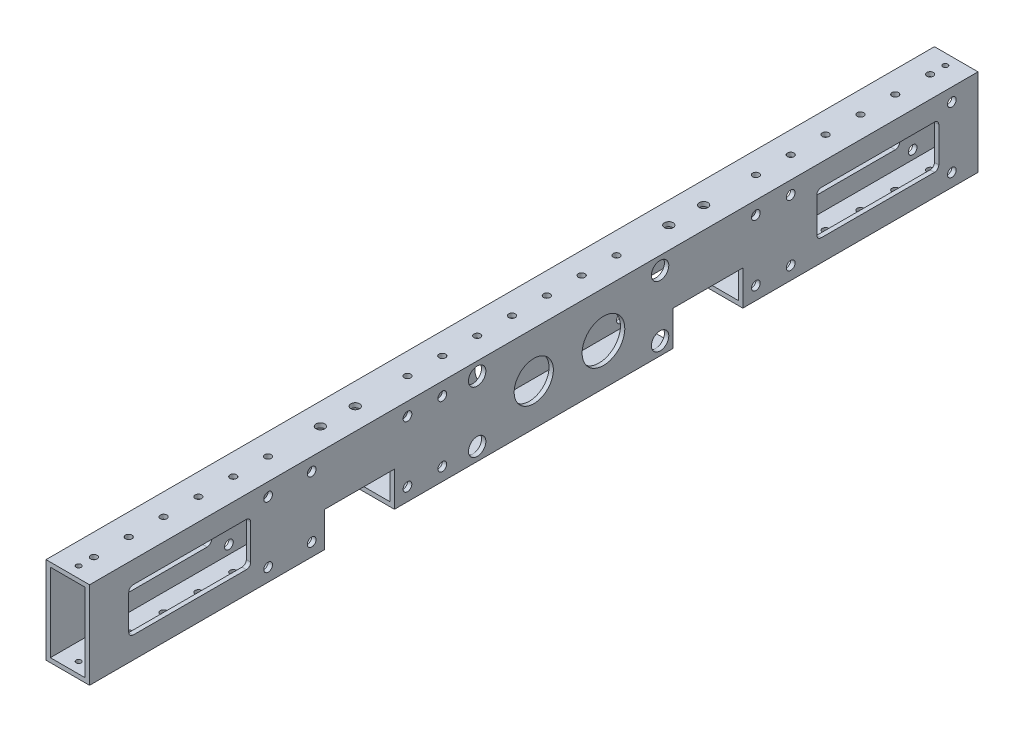
SolidWorks part; units mm, degrees
ref_plane "Front Plane" through (0, 0, 0) normal (0, 0, 1) x (1, 0, 0)
ref_plane "Top Plane" through (0, 0, 0) normal (0, 1, 0) x (1, 0, 0)
ref_plane "Right Plane" through (0, 0, 0) normal (1, 0, 0) x (0, 0, -1)
sketch "Sketch1" plane through (0, 0, 0) normal (0, 0, 1) x (1, 0, 0)
  line L1 (-12.1647, 2.5103) -> (19.5853, 2.5103)
  line L2 (-12.1647, 2.5103) -> (-12.1647, -60.9897)
  line L3 (-12.1647, -60.9897) -> (19.5853, -60.9897)
  line L4 (19.5853, 2.5103) -> (19.5853, -60.9897)
  line L5 (-8.9897, -0.6647) -> (16.4103, -0.6647)
  line L6 (-8.9897, -0.6647) -> (-8.9897, -57.8147)
  line L7 (-8.9897, -57.8147) -> (16.4103, -57.8147)
  line L8 (16.4103, -0.6647) -> (16.4103, -57.8147)
  dimension "D1" = 63.5
  dimension "D2" = 31.75
  dimension "D3" = 3.175
  dimension "D4" = 3.175
  dimension "D5" = 3.175
  dimension "D6" = 3.175
extrude "Boss-Extrude1" add sketch "Sketch1" along normal blind 647.7
sketch "Sketch3" plane through (-12.1647, 0, 0) normal (-1, 0, 0) x (0, 0, 1)
  line L0 (0, 2.5103) -> (0, -60.9897) construction
  line L1 (31.75, -13.3647) -> (114.3, -13.3647)
  line L2 (28.575, -16.5397) -> (28.575, -41.9397)
  line L3 (31.75, -45.1147) -> (114.3, -45.1147)
  line L4 (117.475, -16.5397) -> (117.475, -41.9397)
  line L5 (647.7, 2.5103) -> (0, 2.5103) construction
  line L6 (647.7, -60.9897) -> (0, -60.9897) construction
  line L7 (323.85, 2.5103) -> (323.85, -60.9897) construction
  line L8 (530.225, -16.5397) -> (530.225, -41.9397)
  line L9 (615.95, -45.1147) -> (533.4, -45.1147)
  line L10 (619.125, -16.5397) -> (619.125, -41.9397)
  line L11 (615.95, -13.3647) -> (533.4, -13.3647)
  line L12 (647.7, 2.5103) -> (647.7, -60.9897) construction
  line L13 (171.45, -60.9897) -> (222.25, -60.9897)
  line L14 (171.45, -60.9897) -> (171.45, -35.5897)
  line L15 (171.45, -35.5897) -> (222.25, -35.5897)
  line L16 (222.25, -60.9897) -> (222.25, -35.5897)
  line L17 (425.45, -60.9897) -> (476.25, -60.9897)
  line L18 (476.25, -60.9897) -> (476.25, -35.5897)
  line L19 (476.25, -35.5897) -> (425.45, -35.5897)
  line L20 (425.45, -60.9897) -> (425.45, -35.5897)
  line L22 (0, -29.2397) -> (647.7, -29.2397) construction
  line L23 (0, -60.9897) -> (0, 2.5103) construction
  line L26 (647.7, -60.9897) -> (647.7, 2.5103) construction
  arc A0 (28.575, -41.9397) -> (31.75, -45.1147) centre (31.75, -41.9397) ccw
  arc A1 (114.3, -45.1147) -> (117.475, -41.9397) centre (114.3, -41.9397) ccw
  arc A2 (114.3, -13.3647) -> (117.475, -16.5397) centre (114.3, -16.5397) cw
  arc A3 (31.75, -13.3647) -> (28.575, -16.5397) centre (31.75, -16.5397) ccw
  arc A4 (615.95, -13.3647) -> (619.125, -16.5397) centre (615.95, -16.5397) cw
  arc A5 (533.4, -13.3647) -> (530.225, -16.5397) centre (533.4, -16.5397) ccw
  arc A6 (533.4, -45.1147) -> (530.225, -41.9397) centre (533.4, -41.9397) cw
  arc A7 (619.125, -41.9397) -> (615.95, -45.1147) centre (615.95, -41.9397) cw
  line M7 (0, -60.9897) -> (647.7, -60.9897)
  dimension "D5" = 3.175
  dimension "D1" = 28.575
  dimension "D4" = 88.9
  dimension "D6" = 25.4
  dimension "D7" = 50.8
  dimension "D8" = 171.45
  dimension "D9" = 50.8
  dimension "D10" = 25.4
  dimension "D11" = 171.45
  dimension "D2" = 31.75
  dimension "D3" = 15.875
extrude "Cut-Extrude1" cut sketch "Sketch3" against normal up to surface (31.75 mm away) contours L1 A3 L2 A0 L3 A1 L4 A2 | A7 L10 A4 L11 A5 L8 A6 L9 | L16 L15 L14 M7 | L20 L18 L19 M7 region at (-12.1647, -29.2397, 73.025) region at (-12.1647, -29.2397, 574.675) region at (-12.1647, -48.2897, 196.85) region at (-12.1647, -48.2897, 450.85) up to face at (19.5853, -29.2397, 323.85)
sketch "Sketch6" plane through (19.5853, 0, 0) normal (1, 0, 0) x (0, 0, -1)
  line L0 (-647.7, -30.8272) -> (0, -30.8272) construction
  line L1 (-425.45, -60.9897) -> (-222.25, -60.9897) construction
  line L2 (-365.125, -7.0147) -> (-231.775, -7.0147) construction
  line L3 (-365.125, -7.0147) -> (-365.125, -51.4647) construction
  line L4 (-647.7, -60.9897) -> (-647.7, 2.5103) construction
  line L5 (-365.125, -51.4647) -> (-231.775, -51.4647) construction
  line L6 (-231.775, -7.0147) -> (-231.775, -51.4647) construction
  line L7 (0, -60.9897) -> (0, 2.5103) construction
  circle A0 centre (-323.85, -30.8272) radius 14.2875
  circle A1 centre (-273.05, -30.8272) radius 15.5575
  circle A2 centre (-365.125, -7.0147) radius 3.175
  circle A3 centre (-231.775, -7.0147) radius 3.175
  circle A4 centre (-365.125, -51.4647) radius 3.175
  circle A5 centre (-231.775, -51.4647) radius 3.175
  dimension "D1" = 28.575
  dimension "D4" = 50.8
  dimension "D6" = 20.6375
  dimension "D8" = 41.275
  dimension "D7" = 6.35
  dimension "D10" = 31.115
  dimension "D2" = 30.1625
  dimension "D3" = 323.85
  dimension "D5" = 23.8125
  dimension "D9" = 92.075
extrude "Cut-Extrude2" cut sketch "Sketch6" against normal up to surface (31.75 mm away) up to face at (-12.1647, -41.9397, 323.85)
sketch "Sketch7" plane through (19.5853, 0, 0) normal (1, 0, 0) x (0, 0, -1)
  circle A0 centre (-365.125, -7.0147) radius 6.35
  circle A1 centre (-365.125, -51.4647) radius 6.35
  circle A2 centre (-231.775, -51.4647) radius 6.35
  circle A3 centre (-231.775, -7.0147) radius 6.35
  dimension "D1" = 12.7
extrude "Cut-Extrude3" cut sketch "Sketch7" against normal up to surface (28.575 mm away) up to face at (-8.9897, -16.5397, 323.85)
sketch "Sketch8" plane through (0, 2.5103, 0) normal (0, 1, 0) x (1, 0, 0)
  line L0 (-12.1647, -323.85) -> (19.5853, -323.85) construction
  line L1 (-12.1647, -171.45) -> (19.5853, -171.45) construction
  line L2 (-12.1647, -171.45) -> (-12.1647, -222.25) construction
  line L3 (-12.1647, -222.25) -> (19.5853, -222.25) construction
  line L4 (19.5853, -171.45) -> (19.5853, -222.25) construction
  line L5 (3.7103, -476.25) -> (3.7103, -425.45) construction
  line L6 (-12.1647, -647.7) -> (-12.1647, 0) construction
  line L7 (19.5853, -647.7) -> (19.5853, 0) construction
  line L8 (19.5853, 0) -> (-12.1647, 0) construction
  line L9 (3.7103, -171.45) -> (3.7103, -222.25) construction
  line L10 (19.5853, -476.25) -> (19.5853, -425.45) construction
  line L11 (-12.1647, -425.45) -> (19.5853, -425.45) construction
  line L12 (-12.1647, -476.25) -> (-12.1647, -425.45) construction
  line L13 (-12.1647, -476.25) -> (19.5853, -476.25) construction
  circle A0 centre (3.7103, -184.15) radius 3.175
  circle A1 centre (3.7103, -209.55) radius 3.175
  circle A2 centre (3.7103, -438.15) radius 3.175
  circle A3 centre (3.7103, -463.55) radius 3.175
  dimension "D4" = 6.35
  dimension "D1" = 50.8
  dimension "D2" = 31.75
  dimension "D3" = 171.45
  dimension "D5" = 25.4
  dimension "D6" = 12.7
extrude "Cut-Extrude4" cut sketch "Sketch8" against normal through all
sketch "Sketch9" plane through (0, 2.5103, 0) normal (0, 1, 0) x (1, 0, 0)
  line L0 (19.5853, 0) -> (-12.1647, 0) construction
  line L1 (19.5853, -647.7) -> (-12.1647, -647.7) construction
  line L2 (-12.1647, -647.7) -> (-12.1647, 0) construction
  circle A0 centre (3.7103, -639.7625) radius 1.8415
  circle A1 centre (3.7103, -7.9375) radius 1.8415
  dimension "D1" = 7.9375
  dimension "D3" = 3.683
  dimension "D4" = 3.683
  dimension "D2" = 7.9375
  dimension "D5" = 15.875
  dimension "D6" = 15.875
extrude "Cut-Extrude5" cut sketch "Sketch9" against normal up to surface (63.5 mm away) up to face at (3.7103, -60.9897, 561.975)
sketch "Sketch10" plane through (19.5853, 0, 0) normal (1, 0, 0) x (0, 0, -1)
  line L0 (-647.7, 2.5103) -> (0, 2.5103) construction
  line L1 (-527.05, 2.5103) -> (-476.25, 2.5103) construction
  line L2 (-527.05, 2.5103) -> (-527.05, -60.9897) construction
  line L3 (-527.05, -60.9897) -> (-476.25, -60.9897) construction
  line L4 (-476.25, 2.5103) -> (-476.25, -60.9897) construction
  line L5 (-647.7, -60.9897) -> (-476.25, -60.9897) construction
  line L7 (-476.25, -35.5897) -> (-476.25, -60.9897) construction
  line L8 (-415.925, -51.4647) -> (-390.525, -51.4647) construction
  line L9 (-517.525, -7.0147) -> (-485.775, -7.0147) construction
  line L10 (-517.525, -7.0147) -> (-517.525, -51.4647) construction
  line L11 (-517.525, -51.4647) -> (-485.775, -51.4647) construction
  line L12 (-485.775, -7.0147) -> (-485.775, -51.4647) construction
  line L13 (-425.45, -60.9897) -> (-381, -60.9897) construction
  line L14 (-425.45, -60.9897) -> (-425.45, 2.5103) construction
  line L15 (-425.45, 2.5103) -> (-381, 2.5103) construction
  line L16 (-381, -60.9897) -> (-381, 2.5103) construction
  line L17 (-390.525, -51.4647) -> (-390.525, -7.0147) construction
  line L18 (-415.925, -7.0147) -> (-390.525, -7.0147) construction
  line L19 (-415.925, -51.4647) -> (-415.925, -7.0147) construction
  line L20 (-161.925, -51.4647) -> (-136.525, -51.4647) construction
  line L21 (-171.45, -60.9897) -> (-127, -60.9897) construction
  line L22 (-171.45, -60.9897) -> (-171.45, 2.5103) construction
  line L23 (-171.45, 2.5103) -> (-127, 2.5103) construction
  line L24 (-127, -60.9897) -> (-127, 2.5103) construction
  line L25 (-136.525, -51.4647) -> (-136.525, -7.0147) construction
  line L26 (-161.925, -7.0147) -> (-136.525, -7.0147) construction
  line L27 (-161.925, -51.4647) -> (-161.925, -7.0147) construction
  line L28 (-171.45, -60.9897) -> (0, -60.9897) construction
  line L29 (-171.45, -35.5897) -> (-171.45, -60.9897) construction
  line L30 (0, -60.9897) -> (0, 2.5103) construction
  circle A0 centre (-517.525, -7.0147) radius 3.175
  circle A1 centre (-485.775, -7.0147) radius 3.175
  circle A2 centre (-485.775, -51.4647) radius 3.175
  circle A3 centre (-517.525, -51.4647) radius 3.175
  circle A4 centre (-415.925, -7.0147) radius 3.175
  circle A5 centre (-390.525, -7.0147) radius 3.175
  circle A6 centre (-415.925, -51.4647) radius 3.175
  circle A7 centre (-390.525, -51.4647) radius 3.175
  circle A8 centre (-161.925, -7.0147) radius 3.175
  circle A9 centre (-136.525, -7.0147) radius 3.175
  circle A10 centre (-161.925, -51.4647) radius 3.175
  circle A11 centre (-136.525, -51.4647) radius 3.175
  circle A12 centre (-19.05, -7.0147) radius 3.175
  circle A13 centre (-19.05, -51.4647) radius 3.175
  point P52 (0, 0)
  point P55 (0, 0)
  dimension "D2" = 6.35
  dimension "D1" = 50.8
  dimension "D3" = 9.525
  dimension "D5" = 9.525
  dimension "D4" = 9.525
  dimension "D6" = 9.525
  dimension "D7" = 44.45
  dimension "D9" = 44.45
  dimension "D10" = 9.525
  dimension "D11" = 19.05
  dimension "D8" = 9.525
extrude "Cut-Extrude6" cut sketch "Sketch10" against normal through all
sketch "Sketch11" plane through (0, -60.9897, 0) normal (0, -1, 0) x (1, 0, 0)
  line L0 (19.5853, 647.7) -> (19.5853, 476.25) construction
  line L1 (-12.1647, 647.7) -> (19.5853, 647.7) construction
  line L2 (3.7103, 639.7625) -> (3.7103, 628.65) construction
  circle A0 centre (3.7103, 628.65) radius 2.3813
  circle A1 centre (3.7103, 603.25) radius 2.3813
  circle A2 centre (3.7103, 577.85) radius 2.3813
  circle A3 centre (3.7103, 552.45) radius 2.3813
  circle A4 centre (3.7103, 527.05) radius 2.3813
  circle A5 centre (3.7103, 501.65) radius 2.3813
  circle A9 centre (3.7103, 400.05) radius 2.3813
  circle A10 centre (3.7103, 374.65) radius 2.3813
  circle A11 centre (3.7103, 349.25) radius 2.3813
  circle A12 centre (3.7103, 323.85) radius 2.3813
  circle A13 centre (3.7103, 298.45) radius 2.3813
  circle A14 centre (3.7103, 273.05) radius 2.3813
  circle A15 centre (3.7103, 247.65) radius 2.3813
  circle A19 centre (3.7103, 146.05) radius 2.3813
  circle A20 centre (3.7103, 120.65) radius 2.3813
  circle A21 centre (3.7103, 95.25) radius 2.3813
  circle A22 centre (3.7103, 69.85) radius 2.3813
  circle A23 centre (3.7103, 44.45) radius 2.3813
  circle A24 centre (3.7103, 19.05) radius 2.3813
  circle A25 centre (3.7103, 222.25) radius 2.3813 [skipped]
  circle A26 centre (3.7103, 196.85) radius 2.3813 [skipped]
  circle A27 centre (3.7103, 171.45) radius 2.3813 [skipped]
  circle A28 centre (3.7103, 476.25) radius 2.3813 [skipped]
  circle A29 centre (3.7103, 450.85) radius 2.3813 [skipped]
  circle A30 centre (3.7103, 425.45) radius 2.3813 [skipped]
  dimension "D1" = 15.875
  dimension "D2" = 4.7625
  dimension "D3" = 19.05
  dimension "D4" = 25
extrude "Cut-Extrude7" cut sketch "Sketch11" against normal through all
equation "\"D3@Sketch3\"=\"D2@Sketch3\"/2"
equation "\"D5@Sketch10\"=\"D3@Sketch10\""
equation "\"D4@Sketch10\"=\"D3@Sketch10\""
equation "\"D6@Sketch10\"=\"D5@Sketch10\""
